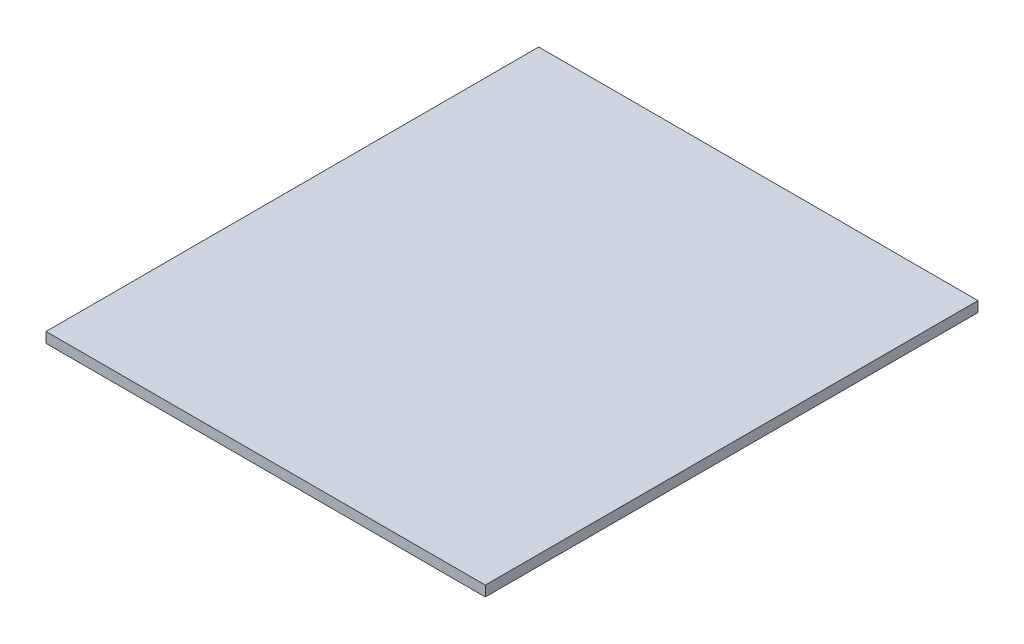
SolidWorks part; units mm, degrees
ref_plane "Front" through (0, 0, 0) normal (0, 0, 1) x (1, 0, 0)
ref_plane "Top" through (0, 0, 0) normal (0, 1, 0) x (1, 0, 0)
ref_plane "Right" through (0, 0, 0) normal (1, 0, 0) x (0, 0, -1)
sketch "Sketch1" plane through (0, 0, 0) normal (0, 1, 0) x (1, 0, 0)
  line L1 (0, 0) -> (255, 0)
  line L2 (0, 0) -> (0, 286)
  line L3 (0, 286) -> (255, 286)
  line L4 (255, 0) -> (255, 286)
  dimension "D1" = 255
  dimension "D2" = 286
extrude "Boss-Extrude1" add sketch "Sketch1" along normal blind 5.9944
